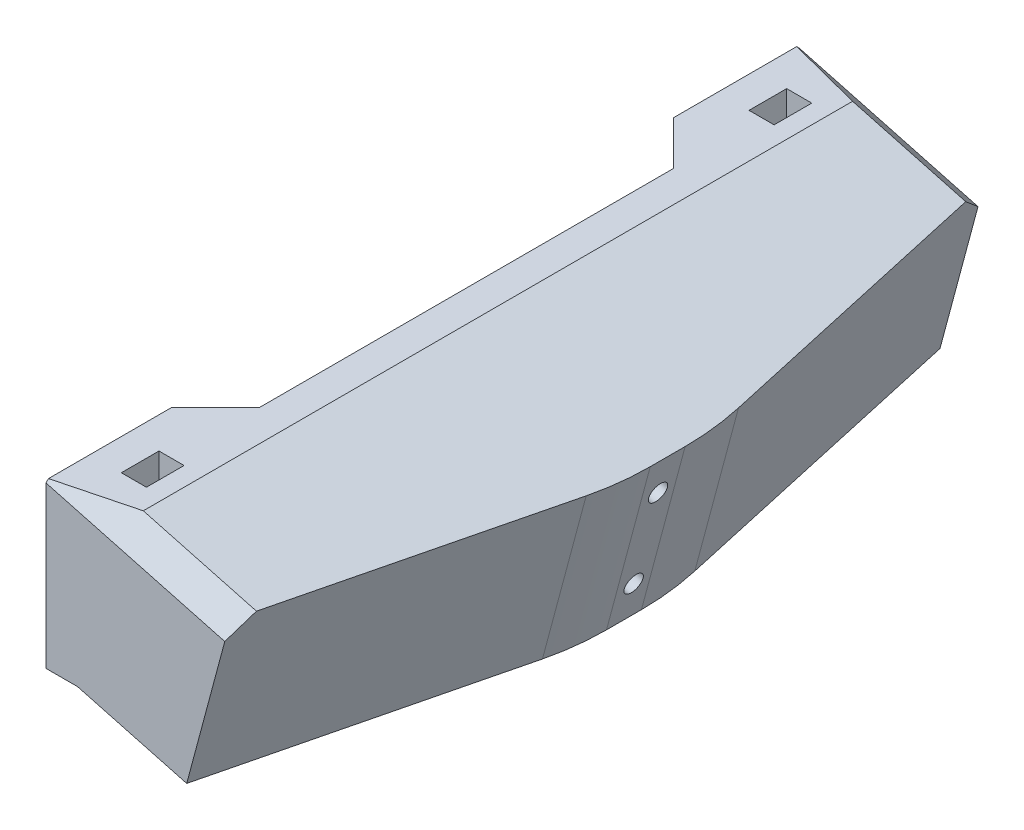
SolidWorks part; units mm, degrees
ref_plane "Front" through (0, 0, 0) normal (0, 0, 1) x (1, 0, 0)
ref_plane "Top" through (0, 0, 0) normal (0, 1, 0) x (1, 0, 0)
ref_plane "Right" through (0, 0, 0) normal (1, 0, 0) x (0, 0, -1)
sketch "Sketch1" plane through (0, 0, 0) normal (0, 0, 1) x (1, 0, 0)
  line L0 (0, 0) -> (0, 26)
  line L1 (0, 26) -> (12, 26)
  line L2 (12, 26) -> (29.3867, 21.3413)
  line L3 (29.3867, 21.3413) -> (22.42, -4.6587)
  line L4 (12, 26) -> (5.0333, 0)
  line L5 (0, 0) -> (5.0333, 0)
  line L6 (5.0333, 0) -> (22.42, -4.6587)
  line L7 (5.0333, 0) -> (5.0333, -8.6951) construction
  dimension "D3" = 18
  dimension "D1" = 26
  dimension "D2" = 12
  dimension "D4" = 75
extrude "Boss-Extrude1" add sketch "Sketch1" against normal blind 120 contours L4 L6 L3 L2 | L0 L5 L4 L1 region at (4.4958, 14.7723, 0) region at (17.21, 10.6706, 0)
sketch "Sketch3" plane through (7.3038, 27.2583, 0) normal (0.2588, 0.9659, 0) x (0.9659, -0.2588, 0)
  line L0 (22.8618, 0) -> (32.8618, 52.5)
  line L1 (32.8618, 52.5) -> (32.8618, 67.5)
  line L2 (32.8618, 67.5) -> (22.8618, 120)
  line L3 (32.8618, 60) -> (22.8618, 60) construction
  line L4 (22.8618, 120) -> (22.8618, 0) construction
  line L5 (22.8618, 120) -> (22.8618, 0)
  dimension "D1" = 10
  dimension "D2" = 15
extrude "Boss-Extrude2" add sketch "Sketch3" against normal up to surface (26.9172 mm away) up to face at (13.7267, -2.3294, -60)
sketch "Sketch6" plane through (0, 26, 0) normal (0, 1, 0) x (1, 0, 0)
  line L0 (0, 100) -> (7, 93)
  line L21 (0, 120) -> (0, 0) construction
  line L22 (7, 93) -> (7, 27)
  line L25 (7, 27) -> (0, 20)
  line L26 (0, 120) -> (12, 120) construction
  line L31 (0, 100) -> (0, 20)
  dimension "D1" = 45
  dimension "D2" = 45
  dimension "D3" = 7
  dimension "D4" = 20
  dimension "D5" = 20
extrude "Cut-Extrude3" cut sketch "Sketch6" against normal through all
sketch "Sketch7" plane through (0, 0, 0) normal (-1, 0, 0) x (0, 0, 1)
  line L0 (-120, 0) -> (-120, 26) construction
  line L1 (0, 0) -> (0, 26) construction
  line L2 (-120, 0) -> (-100, 0) construction
  circle A0 centre (-110, 15) radius 1.55
  circle A1 centre (-10, 15) radius 1.55
  dimension "D1" = 3.1
  dimension "D2" = 3.1
  dimension "D4" = 10
  dimension "D5" = 15
  dimension "D3" = 10
extrude "Cut-Extrude4" cut sketch "Sketch7" against normal blind 10
ref_plane "Plane2" through (5, 0, 0) normal (-1, 0, 0) x (0, 0, 1)
sketch "Sketch8" plane through (5, 0, 0) normal (-1, 0, 0) x (0, 0, 1)
  line L0 (-113, 16.7321) -> (-113, 26)
  line L1 (-111.5, 17.5981) -> (-113, 16.7321)
  line L2 (-113, 16.7321) -> (-113, 13.2679)
  line L3 (-113, 13.2679) -> (-110, 11.5359)
  line L4 (-110, 11.5359) -> (-107, 13.2679)
  line L5 (-107, 13.2679) -> (-107, 16.7321)
  line L6 (-107, 16.7321) -> (-108.5, 17.5981)
  line L7 (-120, 26) -> (-100, 26) construction
  line L8 (-113, 26) -> (-107, 26)
  line L9 (-107, 26) -> (-107, 16.7321)
  line L10 (-60, 26) -> (-60, 24.3172) construction
  line L11 (-27, 26) -> (-93, 26) construction
  line L12 (-13, 26) -> (-13, 16.7321)
  line L13 (-7, 26) -> (-13, 26)
  line L14 (-13, 16.7321) -> (-11.5, 17.5981)
  line L15 (-13, 13.2679) -> (-13, 16.7321)
  line L16 (-10, 11.5359) -> (-13, 13.2679)
  line L17 (-7, 13.2679) -> (-10, 11.5359)
  line L18 (-7, 16.7321) -> (-7, 13.2679)
  line L19 (-8.5, 17.5981) -> (-7, 16.7321)
  line L20 (-7, 16.7321) -> (-7, 26)
  circle A0 centre (-110, 15) radius 3 construction
  circle A1 centre (-10, 15) radius 3 construction
  dimension "D1" = 6
extrude "Cut-Extrude5" cut sketch "Sketch8" against normal blind 4 contours L9 L8 L0 L2 L3 L4 L5 | L20 L13 L12 L15 L16 L17 L18 region at (5, 19.1918, -110) region at (5, 19.1918, -10)
fillet "Fillet1" radius 50 2 edges at (35.5626, 5.7531, -67.5) (35.5626, 5.7531, -52.5)
sketch "Sketch10" plane through (31.7421, -8.5053, 0) normal (0.9659, -0.2588, 0) x (0, 0, -1)
  line L1 (62.7805, 14.7613) -> (57.2195, 14.7613) construction
  line L2 (62.7805, 1.3027) -> (62.7805, 28.2199) construction
  line L3 (60, 22.2613) -> (60, 7.2613) construction
  line L4 (57.2195, 28.2199) -> (57.2195, 1.3027) construction
  circle A0 centre (60, 22.2613) radius 1.5
  circle A1 centre (60, 7.2613) radius 1.5
  point P11 (60, 14.7613)
  dimension "D1" = 3
  dimension "D2" = 3
  dimension "D3" = 15
extrude "Cut-Extrude6" cut sketch "Sketch10" against normal through all
chamfer "Chamfer4" distance 3.5 angle 45 2 edges at (20.6933, 23.6706, -120) (20.6933, 23.6706, 0)
ref_plane "Plane3" through (-2.0653, 0.5534, 0) normal (0.9659, -0.2588, 0) x (0, 0, -1)
sketch "Sketch12" plane through (-2.0653, 0.5534, 0) normal (0.9659, -0.2588, 0) x (0, 0, -1)
  circle A0 centre (60, 22.2613) radius 4
  circle A1 centre (60, 7.2613) radius 4
  dimension "D1" = 8
  dimension "D2" = 8
extrude "Cut-Extrude8" cut sketch "Sketch12" along normal blind 5 contours A0 region at (3.6963, 22.0562, -60)
extrude "Cut-Extrude9" cut sketch "Sketch12<3>" along normal blind 9 contours A1 region at (-0.186, 7.5673, -60)
sketch "Sketch12<3>" plane through (-2.0653, 0.5534, 0) normal (0.9659, -0.2588, 0) x (0, 0, -1) same geometry as "Sketch12"
